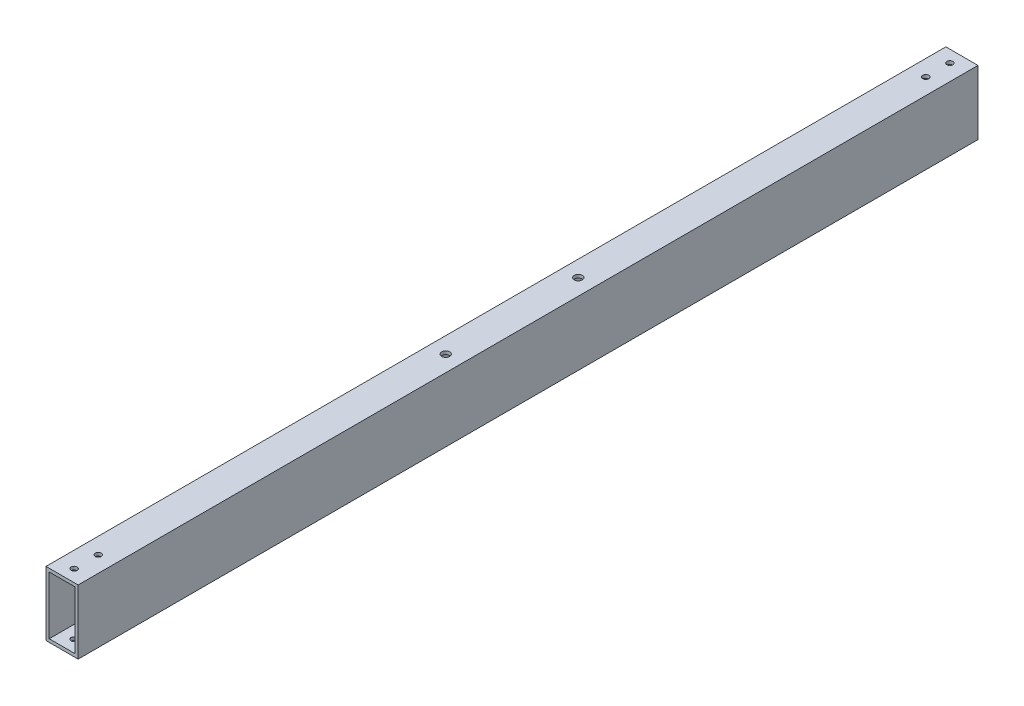
SolidWorks part; units mm, degrees
ref_plane "Front Plane" through (0, 0, 0) normal (0, 0, 1) x (1, 0, 0)
ref_plane "Top Plane" through (0, 0, 0) normal (0, 1, 0) x (1, 0, 0)
ref_plane "Right Plane" through (0, 0, 0) normal (1, 0, 0) x (0, 0, -1)
sketch "Sketch1" plane through (0, 0, 0) normal (0, 0, 1) x (1, 0, 0)
  line L1 (12.7, 25.4) -> (-12.7, 25.4)
  line L2 (12.7, 25.4) -> (12.7, -25.4)
  line L3 (12.7, -25.4) -> (-12.7, -25.4)
  line L4 (-12.7, 25.4) -> (-12.7, -25.4)
  line L5 (0, -25.4) -> (0, 25.4) construction
  line L6 (12.7, 0) -> (-12.7, 0) construction
  point P0 (0, 0)
  dimension "D1" = 25.4
  dimension "D2" = 50.8
extrude "Boss-Extrude1" add sketch "Sketch1" along normal mid plane 711.2
shell "Shell1" thickness 2.54 removed face at (0, 0, -355.6) removed face at (0, 0, 355.6)
sketch "Sketch2" plane through (0, -25.4, 0) normal (0, -1, 0) x (1, 0, 0)
  line L0 (-12.7, 355.6) -> (12.7, 355.6) construction
  line L1 (0, 0) -> (110.7083, 0) construction
  circle A0 centre (0, 346.075) radius 2.3813
  circle A1 centre (0, 327.025) radius 2.3813
  circle A4 centre (0, -327.025) radius 2.3813
  circle A5 centre (0, -346.075) radius 2.3813
  point P13 (110.7083, 0)
  dimension "D1" = 19.05
  dimension "D3" = 4.7625
  dimension "D2" = 9.525
extrude "Cut-Extrude1" cut sketch "Sketch2" against normal through all
sketch "Sketch3" plane through (0, -25.4, 0) normal (0, -1, 0) x (1, 0, 0)
  line L0 (0, 0) -> (105.4647, 0) construction
  circle A0 centre (0, 52.3875) radius 3.175
  circle A1 centre (0, -52.3875) radius 3.175
  point P7 (0, 0)
  point P8 (0, 0)
  dimension "D1" = 6.35
  dimension "D2" = 104.775
extrude "Cut-Extrude2" cut sketch "Sketch3" against normal through all
